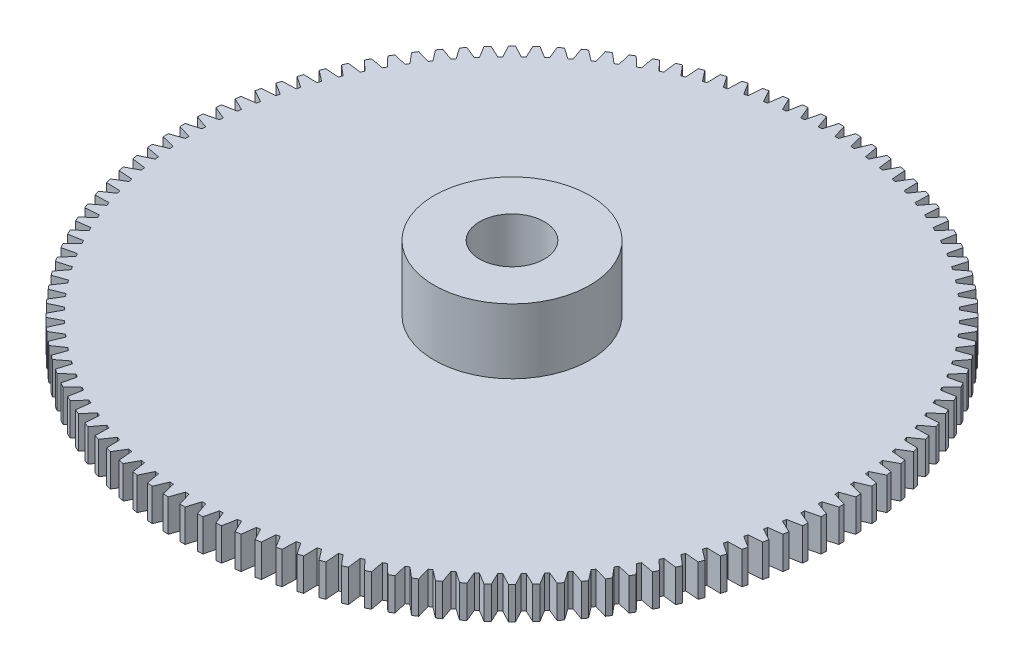
SolidWorks part; units mm, degrees
ref_plane "Front Plane" through (0, 0, 0) normal (0, 0, 1) x (1, 0, 0)
ref_plane "Top Plane" through (0, 0, 0) normal (0, 1, 0) x (1, 0, 0)
ref_plane "Right Plane" through (0, 0, 0) normal (1, 0, 0) x (0, 0, -1)
sketch "Sketch1" plane through (0, 0, 0) normal (0, 1, 0) x (1, 0, 0)
  circle A0 centre (0, 0) radius 3.175
  circle A1 centre (0, 0) radius 7.62
  dimension "D1" = 6.35
  dimension "D2" = 15.24
extrude "Boss-Extrude1" add sketch "Sketch1" along normal blind 9.525 contours A1 A0 region at (-7.4045, 0, 0)
sketch "Sketch2" plane through (0, 0, 0) normal (0, 1, 0) x (1, 0, 0)
  line L0 (0, 0) -> (0, 30.988) construction
  line L1 (-0.635, 30.9815) -> (0.635, 30.9815)
  line L2 (0, 30.988) -> (0, 32.258) construction
  line L3 (-0.254, 32.258) -> (0.254, 32.258)
  line L4 (-0.254, 32.258) -> (-0.635, 30.9815)
  line L5 (0.254, 32.258) -> (0.635, 30.9815)
  circle A0 centre (0, 0) radius 30.988
  point P11 (0, 32.258)
  dimension "D1" = 61.976
  dimension "D2" = 1.27
  dimension "D3" = 1.27
  dimension "D4" = 0.508
extrude "Boss-Extrude2" add sketch "Sketch2" along normal blind 3.175 contours L1 A0 region at (0, 0, 0.0001)
extrude "Boss-Extrude3" add sketch "Sketch2<3>" along normal blind 3.175 contours L5 L1 L4 L3
sketch "Sketch2<3>" plane through (0, 0, 0) normal (0, 1, 0) x (1, 0, 0) same geometry as "Sketch2"
pattern_circular "CirPattern1" count 120 over 360 about axis through (0, 9.525, 0) along (0, -1, 0) of "Boss-Extrude3" reverse direction yes
equation "\"Number_Teeth\" = 120"
equation "\"Diametral_Pitch\" = 48"
equation "\"Pitch_Diameter\"= \"Number_Teeth\" * \"1_inch\" / \"Diametral_Pitch\""
equation "\"Tooth_Height\"= .05in"
equation "\"Addendum\"= \"Tooth_Height\" * .4"
equation "\"Dedendum\"= \"Tooth_Height\" * .6"
equation "\"D1@Sketch2\"=\"Pitch_Diameter\"-(2*\"Dedendum\")"
equation "\"D3@Sketch2\"=\"Tooth_Height\""
equation "\"1_inch\"= 1in"
equation "\"D1@CirPattern1\"=\"Number_Teeth\""
